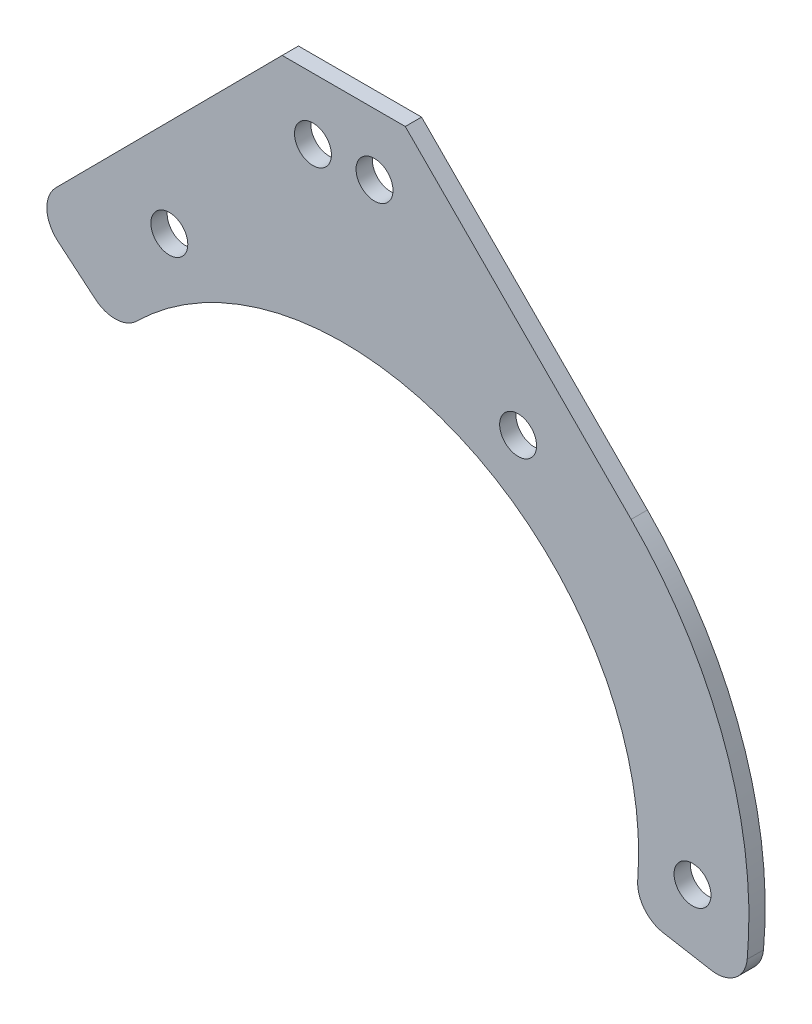
SolidWorks part; units mm, degrees
ref_plane "Front Plane" through (0, 0, 0) normal (0, 0, 1) x (1, 0, 0)
ref_plane "Top Plane" through (0, 0, 0) normal (0, 1, 0) x (1, 0, 0)
ref_plane "Right Plane" through (0, 0, 0) normal (1, 0, 0) x (0, 0, -1)
sketch "Sketch1" plane through (0, 0, 0) normal (0, 0, 1) x (1, 0, 0)
  circle A0 centre (0, 0) radius 39.5
  dimension "OuterDiam" = 79
extrude "Boss-Extrude1" add sketch "Sketch1" along normal mid plane 1.5875
sketch "Sketch3" plane through (0, 0, 0.7937) normal (0, 0, 1) x (1, 0, 0)
  line L0 (0, 50) -> (0, 0) construction
  line L2 (-28.0184, 27.8428) -> (-6, 50)
  line L3 (-6, 50) -> (6, 50)
  line L4 (28.0184, 27.8428) -> (6, 50)
  line L5 (-16.4342, 39.5) -> (16.4342, 39.5) construction
  line L6 (-28.0184, 27.8428) -> (28.0184, 27.8428)
  circle A1 centre (0, 0) radius 39.5 construction
  dimension "TopToHipAdductionCenter" = 10.5
  dimension "MotorCenterToAdductionCenter" = 39.5
  dimension "TopWidth" = 12
extrude "Boss-Extrude2" add sketch "Sketch3" against normal through all
sketch "Sketch4" plane through (0, 0, 0.7937) normal (0, 0, 1) x (1, 0, 0)
  line L0 (0, 50) -> (0, 0) construction
  line L1 (0, 47) -> (0, 32) construction
  line L2 (-16.4342, 39.5) -> (16.4342, 39.5) construction
  circle A0 centre (0, 47) radius 2.7
  circle A1 centre (0, 32) radius 2.7
  point P8 (0, 39.5)
  dimension "D2" = 5.4
  dimension "D1" = 15
extrude "Cut-Extrude2" [suppressed] cut sketch "Sketch4" against normal through all
sketch "Sketch2" plane through (0, 0, 0.7937) normal (0, 0, 1) x (1, 0, 0)
  circle A0 centre (0, 0) radius 28.75
  dimension "ElectronicsCutoutDiam" = 57.5
extrude "Cut-Extrude1" cut sketch "Sketch2" against normal through all
hole_wizard "M3 Clearance Hole1" positions "Sketch5" profile "Sketch6" hole size "M3" standard "ANSI Metric" end condition through all
sketch "Sketch5" plane through (0, 0, 0.7937) normal (0, 0, 1) x (1, 0, 0)
  line L7 (0, 0) -> (0, -28.75) construction
  line L10 (0, 0) -> (17, -29.4449) construction
  circle A1 centre (0, 0) radius 28.75 construction
  circle A2 centre (0, 0) radius 34 construction
  point P6 (17, -29.4449)
  dimension "MotorMountPatternDiam" = 68
  dimension "HoleAngleFromVert" = 30
sketch "Sketch6" plane through (17, -29.4449, 0.7937) normal (1, 0, 0) x (0, -1, 0)
  line L0 (0, 0) -> (0, 1.5875)
  line L1 (0, 1.5875) -> (1.8, 1.5875)
  line L2 (1.8, 1.5875) -> (1.8, 0)
  line L5 (1.8, 0) -> (0, 0)
  line L11 (0, -6.35) -> (0, 107.95) construction
  dimension "Thru Hole Dia." = 3.6
  dimension "Thru Hole Depth" = 1.5875
pattern_circular "CirPattern1" count 6 over 360 about axis through (0, 0, 0.7937) along (0, 0, 1) of "M3 Clearance Hole1"
hole_wizard "M3 Clearance Hole2" positions "Sketch7" profile "Sketch8" hole size "M3" standard "ANSI Metric"
sketch "Sketch7" plane through (0, 0, 0.7937) normal (0, 0, 1) x (1, 0, 0)
  line L0 (0, 50) -> (0, 39.5) construction
  line L1 (6, 50) -> (-6, 50) construction
  line L4 (-3, 44) -> (3, 44) construction
  line L5 (-6, 50) -> (6, 50) construction
  circle A0 centre (0, 0) radius 39.5 construction
  point P11 (-3, 44)
  point P12 (3, 44)
  point P17 (0, 44.75)
  point P21 (0, 44)
  dimension "D1" = 6
  dimension "D2" = 6
sketch "Sketch8" plane through (3, 44, 0.7937) normal (1, 0, 0) x (0, -1, 0)
  line L0 (0, 0) -> (0, 11.0815)
  line L1 (0, 11.0815) -> (1.8, 10)
  line L2 (1.8, 10) -> (1.8, 0)
  line L5 (1.8, 0) -> (0, 0)
  line L10 (0, 11.0815) -> (-1.8, 10) construction
  line L11 (0, -6.35) -> (0, 107.95) construction
  dimension "Hole Dia." = 3.6
  dimension "Hole Depth" = 10
  dimension "Drill Angle" = 118
sketch "OpenEdge" plane through (0, 0, -0.7937) normal (0, 0, -1) x (-1, 0, 0)
  line L0 (0, 0) -> (0, -39.5) construction
  line L1 (22.0238, 18.4801) -> (30.2588, 25.3901)
  line L2 (-28.3132, -4.9924) -> (-38.8999, -6.8591)
  circle A0 centre (0, 0) radius 39.5 construction
  circle A1 centre (0, 0) radius 28.75 construction
  circle A2 centre (0, 0) radius 28.75 construction
  arc A3 (-28.3132, -4.9924) -> (22.0238, 18.4801) centre (0, 0) ccw
  arc A4 (-38.8999, -6.8591) -> (30.2588, 25.3901) centre (0, 0) ccw
  dimension "frontAngle" = 130
  dimension "backAngle" = 80
extrude "Cut-Extrude3" cut sketch "OpenEdge" against normal through all
fillet "Fillet1" radius 3 4 edges at (38.8999, -6.8591, 0) (28.3132, -4.9924, 0) (-30.2588, 25.3901, 0) (-22.0238, 18.4801, 0)
ref_axis "Axis1" through (34, 0, -0.7937) along (0, 0, 1)
ref_axis "Axis2" through (17, 29.4449, -0.7937) along (0, 0, 1)
ref_axis "Axis3" through (-17, 29.4449, -0.7937) along (0, 0, 1)
ref_axis "Axis4" through (34, 0, -0.7937) along (0, 0, 1)
ref_axis "Axis5" through (17, 29.4449, -0.7937) along (0, 0, 1)
ref_axis "Axis6" through (-17, 29.4449, -0.7937) along (0, 0, 1)
ref_axis "Axis7" [suppressed] through (-34, 0, -0.7937) along (0, 0, 1)
ref_axis "Axis8" [suppressed] through (17, -29.4449, -0.7937) along (0, 0, 1)
ref_axis "Axis9" [suppressed] through (-17, -29.4449, -0.7937) along (0, 0, 1)
